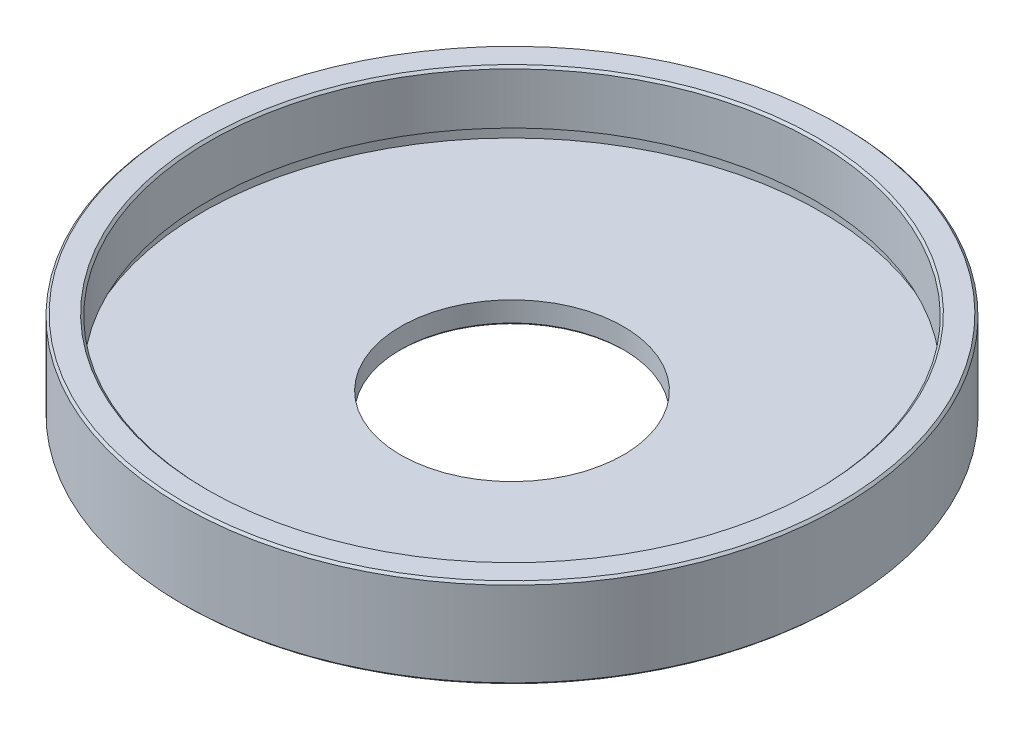
SolidWorks part; units mm, degrees
material "AISI 304"
ref_plane "Спереди" through (0, 0, 0) normal (0, 0, 1) x (1, 0, 0)
ref_plane "Сверху" through (0, 0, 0) normal (0, 1, 0) x (1, 0, 0)
ref_plane "Справа" through (0, 0, 0) normal (1, 0, 0) x (0, 0, -1)
ref_axis "ОсьX" through (-88.99, 0, 0) along (1, 0, 0)
ref_axis "ОсьZ" through (0, 55, 0) along (0, -1, 0)
ref_axis "ОсьY" through (0, 0, -88.99) along (0, 0, 1)
sketch "Эскиз1" plane through (0, 0, 0) normal (0, 0, 1) x (1, 0, 0)
  line L0 (-74, 20) -> (-74, 0)
  line L1 (0, 26.169) -> (0, -22.1581) construction
  line L2 (-74, 0) -> (-25, 0)
  line L3 (-25, 0) -> (-25, 5)
  line L4 (-25, 5) -> (-69.5, 5)
  line L6 (-69.5, 8) -> (-68, 8)
  line L7 (-68, 8) -> (-68, 20)
  line L8 (-68, 20) -> (-74, 20)
  line L11 (-69.5, 8) -> (-69.5, 5)
  dimension "D1" = 148
  dimension "D2" = 20
  dimension "D3" = 136
  dimension "D4" = 50
  dimension "D5" = 5
  dimension "D6" = 1.5
  dimension "D9" = 12
revolve "Повернуть1" add sketch "Эскиз1" angle 360 mid plane about L1
chamfer "Фаска1" distance 0.5 angle 45 4 edges at (0, 0, 25) (0, 0, 74) (0, 20, 74) (0, 20, 68)
